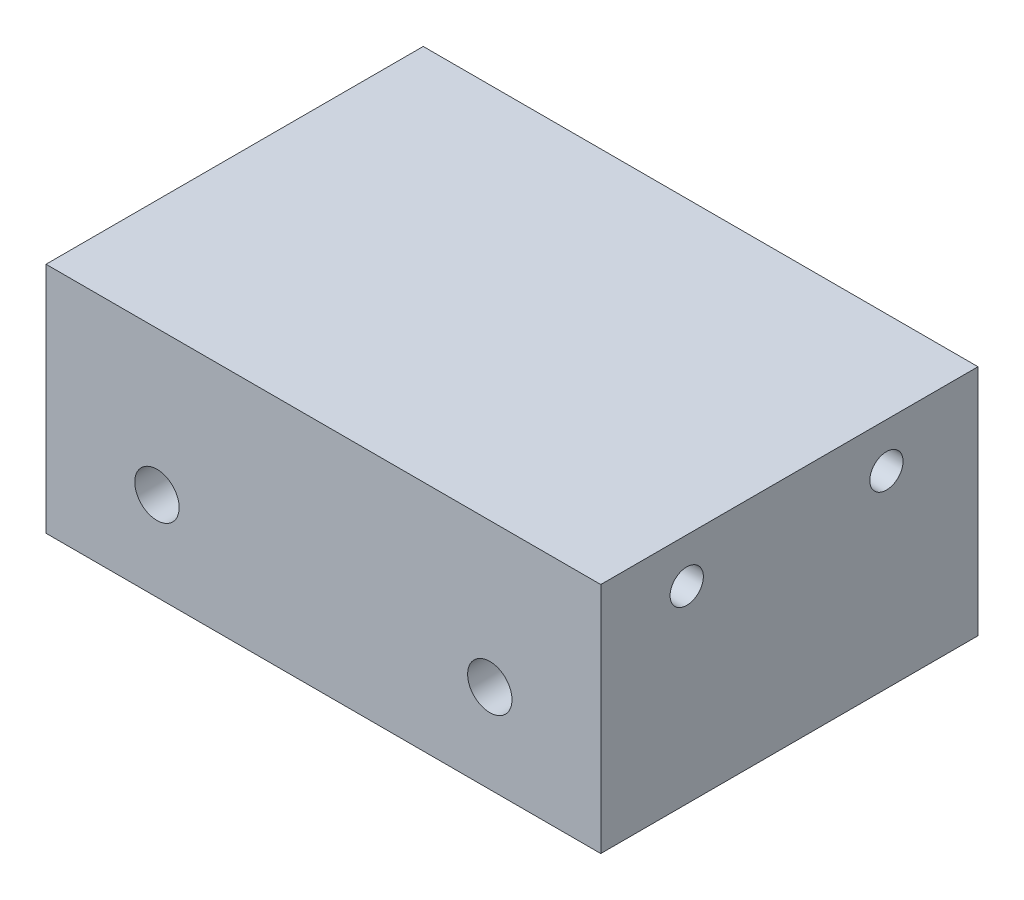
SolidWorks part; units mm, degrees
ref_plane "Front" through (0, 0, 0) normal (0, 0, 1) x (1, 0, 0)
ref_plane "Top" through (0, 0, 0) normal (0, 1, 0) x (1, 0, 0)
ref_plane "Right" through (0, 0, 0) normal (1, 0, 0) x (0, 0, -1)
sketch "草图1" plane through (0, 0, 0) normal (0, 0, 1) x (1, 0, 0)
  line L0 (35, -3) -> (-25, -3) construction
  line L1 (25, -3) -> (-25, -3)
  line L2 (25, -24) -> (25, 0) construction
  line L3 (-25, -24) -> (25, -24) construction
  line L4 (-25, -24) -> (-25, 0) construction
  line L5 (25, -24) -> (25, -3)
  line L6 (-25, -24) -> (25, -24)
  line L7 (-25, -24) -> (-25, -3)
extrude "凸台-拉伸1" add sketch "草图1" along normal up to surface (34 mm away) contours L6 L5 L1 L7
sketch "草图2" plane through (0, 0, 0) normal (0, 0, -1) x (-1, 0, 0)
  circle A0 centre (-15, -16) radius 2 construction
  circle A1 centre (15, -16) radius 2 construction
  circle A2 centre (-15, -16) radius 2
  circle A3 centre (15, -16) radius 2
extrude "切除-拉伸1" cut sketch "草图2" against normal through all
sketch "草图3" plane through (-25, 0, 0) normal (-1, 0, 0) x (0, 0, 1)
  circle A2 centre (8.2526, -7) radius 1.5
  circle A3 centre (26.2526, -7) radius 1.5
extrude "切除-拉伸2" cut sketch "草图3" against normal through all
